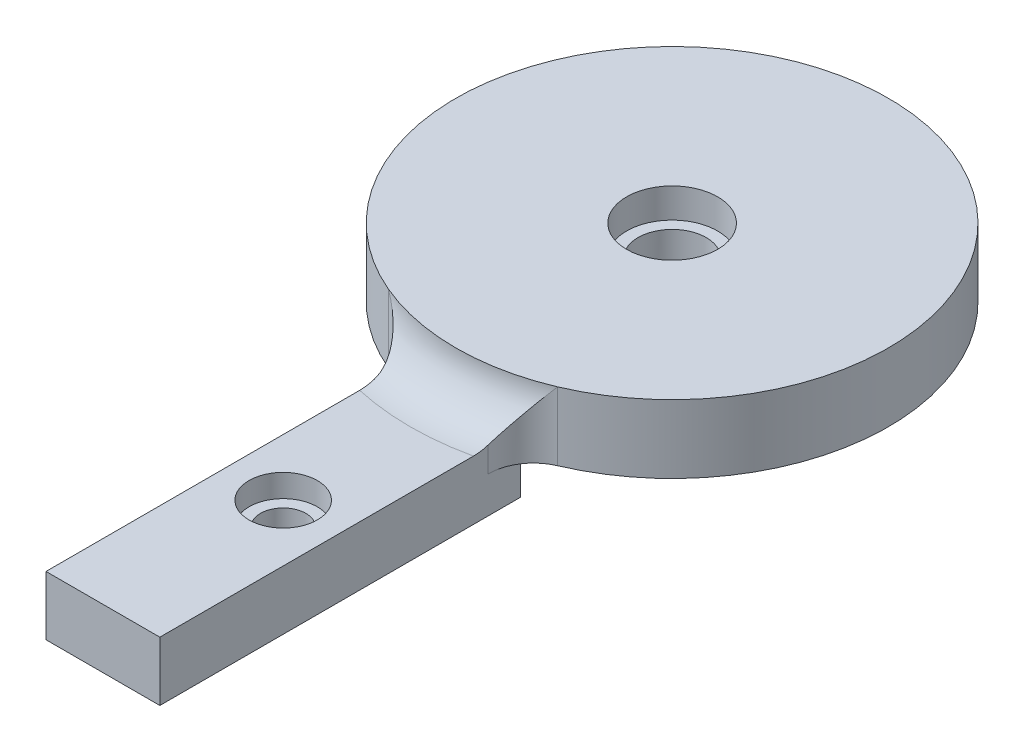
SolidWorks part; units mm, degrees
ref_plane "前视基准面" through (0, 0, 0) normal (0, 0, 1) x (1, 0, 0)
ref_plane "上视基准面" through (0, 0, 0) normal (0, 1, 0) x (1, 0, 0)
ref_plane "右视基准面" through (0, 0, 0) normal (1, 0, 0) x (0, 0, -1)
other "Configuration Table"
sketch "草图1" plane through (0, 0, 0) normal (0, 1, 0) x (1, 0, 0)
  circle A0 centre (0, 0) radius 9.5
  dimension "D1" = 19
extrude "凸台-拉伸1" add sketch "草图1" along normal blind 3 contours A0
sketch "草图2" plane through (0, 0, 0) normal (0, -1, 0) x (-1, 0, 0)
  circle A0 centre (0, 0) radius 7.6
  dimension "D1" = 15.2
extrude "切除-拉伸1" cut sketch "草图2" against normal blind 0.5
sketch "草图3" plane through (0, 0, 0) normal (0, -1, 0) x (1, 0, 0)
  line L1 (-2.5, 0) -> (2.5, 0)
  line L2 (-2.5, 0) -> (-2.5, 25)
  line L3 (-2.5, 25) -> (2.5, 25)
  line L4 (2.5, 0) -> (2.5, 25)
  circle A0 centre (0, 0) radius 9.5
  circle A2 centre (0, 0) radius 9.5 construction
  circle M5 centre (0, 0) radius 9.5
  dimension "D1" = 5
  dimension "D2" = 25
extrude "凸台-拉伸2" add sketch "草图3" along normal blind 2.6 from offset 1 contours L4 L3 L2 M5 region at (0, 0, 17.1943) offset against normal yes
sketch "草图5" plane through (0, 3, 0) normal (0, 1, 0) x (1, 0, 0)
  circle A0 centre (0, 0) radius 2
  circle A1 centre (0, 0) radius 1.5
  dimension "D1" = 3
  dimension "D2" = 4
extrude "切除-拉伸3" cut sketch "草图5" against normal blind 1.3 contours A0
extrude "切除-拉伸4" cut sketch "草图5<3>" against normal through all contours A1
sketch "草图5<3>" plane through (0, 3, 0) normal (0, 1, 0) x (1, 0, 0) same geometry as "草图5"
sketch "草图6" plane through (0, 1, 0) normal (0, 1, 0) x (1, 0, 0)
  line L0 (-2.5, -17.0826) -> (2.5, -17.0826) construction
  line L1 (-2.5, -9.1652) -> (-2.5, -25) construction
  line L2 (2.5, -9.1652) -> (2.5, -25) construction
  circle A0 centre (0, -17.0826) radius 1.5
  circle A1 centre (0, -17.0826) radius 1
  dimension "D1" = 3
  dimension "D2" = 2
extrude "切除-拉伸5" cut sketch "草图6" against normal blind 1 contours A0
extrude "切除-拉伸6" cut sketch "草图6<3>" against normal through all contours A1
sketch "草图6<3>" plane through (0, 1, 0) normal (0, 1, 0) x (1, 0, 0) same geometry as "草图6"
fillet "圆角1" radius 2 1 edges at (0, 1, 9.5)
fillet "圆角2" radius 2 2 edges at (-2.5, 1.5, 9.1652) (2.5, 1.5, 9.1652)
